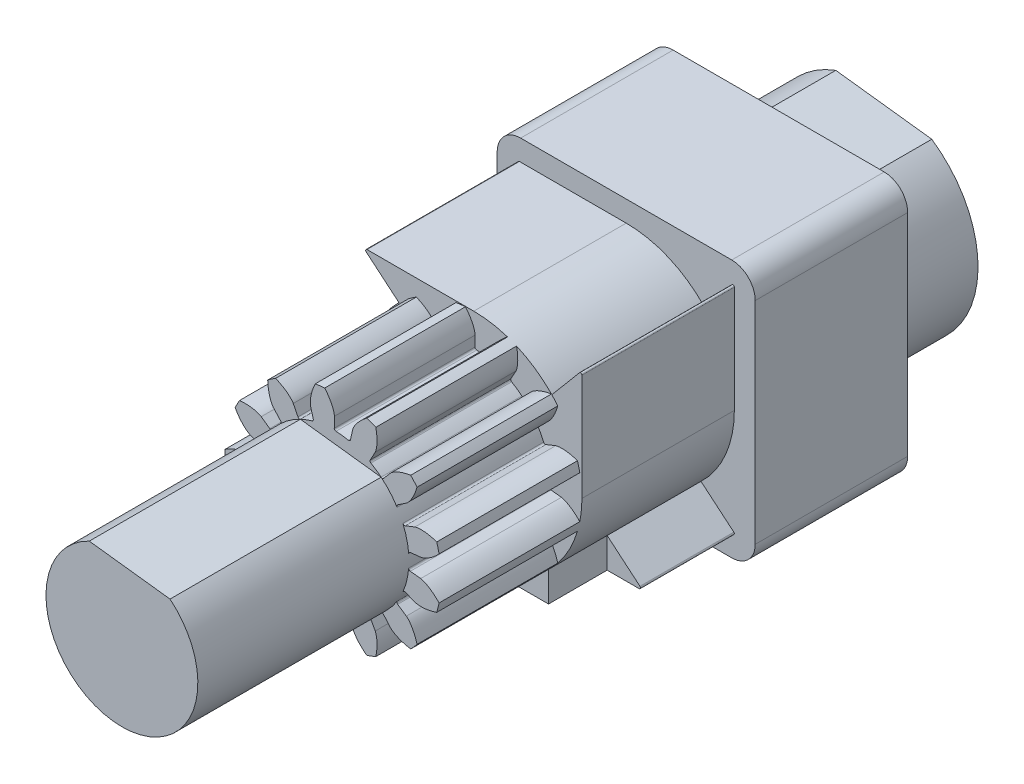
SolidWorks part; units mm, degrees
ref_plane "Front Plane" through (0, 0, 0) normal (0, 0, 1) x (1, 0, 0)
ref_plane "Top Plane" through (0, 0, 0) normal (0, 1, 0) x (1, 0, 0)
ref_plane "Right Plane" through (0, 0, 0) normal (1, 0, 0) x (0, 0, -1)
sketch "D" plane through (0, 0, 0) normal (0, 0, 1) x (1, 0, 0)
  line L0 (0, 0) -> (16, 0) construction
  circle A0 centre (0, 0) radius 4 construction
  dimension "D2" = 16
sketch "De, Di, Db" plane through (0, 0, 0) normal (0, 0, 1) x (1, 0, 0)
  circle A0 centre (0, 0) radius 3.7588 construction
  circle A1 centre (0, 0) radius 4.61 construction
  circle A2 centre (0, 0) radius 3.2375 construction
  point P7 (0, 0)
  dimension "D1" = 7.5175
  dimension "D2" = 9.22
  dimension "D3" = 6.475
sketch "Sketch4" plane through (0, 0, 0) normal (0, 0, 1) x (1, 0, 0)
  circle A0 centre (0, 0) radius 4.61 construction
  circle A1 centre (0, 0) radius 4.61
extrude "Addendum Extruded" add sketch "Sketch4" along normal mid plane 6
sketch "Tooth Profile Curve" plane through (0, 0, 0) normal (0, 0, 1) x (1, 0, 0)
  line L0 (0, 0) -> (4.61, 0) construction
  line L1 (0, 0) -> (3.7381, 0.3937) construction
  line L2 (0, 0) -> (3.9713, 0.4779) construction
  line L3 (3.7381, 0.3937) -> (3.2197, 0.3391)
  line L4 (3.2375, 0) -> (4.61, 0)
  circle A0 centre (0, 0) radius 3.7588 construction
  circle A1 centre (0, 0) radius 4.61 construction
  circle A2 centre (0, 0) radius 3.2375 construction
  circle A3 centre (0, 0) radius 4 construction
  arc A4 (3.2197, 0.3391) -> (3.2375, 0) centre (0, 0) cw
  arc A5 (4.61, 0) -> (4.5206, 0.9037) centre (0, 0) ccw
  spline S0 degree 4 poles (3.7381, 0.3937) (3.7409, 0.3941) (3.7486, 0.3952) (3.763, 0.3981) (3.7864, 0.4038) (3.8294, 0.4166) (3.8801, 0.4354) (3.9361, 0.4599) (3.995, 0.4897) (4.0445, 0.5171) (4.093, 0.5463) (4.1404, 0.5771) (4.1969, 0.6162) (4.2631, 0.6658) (4.3382, 0.7275) (4.4204, 0.8017) (4.501, 0.8819) (4.5775, 0.9643) (4.6515, 1.0515) (4.7207, 1.1386) (4.7888, 1.2329) (4.8499, 1.3219) (4.9141, 1.4255) (4.9647, 1.5102) (5.0267, 1.626) (5.062, 1.6955) (5.1015, 1.7782) (5.1182, 1.8155) (5.1285, 1.8385) knots 0 0 0 0 0 0.005377 0.015084 0.028532 0.04661 0.092111 0.119476 0.146842 0.174209 0.201575 0.228941 0.256307 0.307035 0.361767 0.4165 0.471232 0.525964 0.580697 0.635429 0.690161 0.744894 0.799626 0.854358 0.909091 0.954545 1 1 1 1 1 construction
  spline S1 degree 4 poles (3.7381, 0.3937) (3.7409, 0.3941) (3.7486, 0.3952) (3.763, 0.3981) (3.7864, 0.4038) (3.8294, 0.4166) (3.8801, 0.4354) (3.9361, 0.4599) (3.995, 0.4897) (4.0445, 0.5171) (4.093, 0.5463) (4.1404, 0.5771) (4.1969, 0.6162) (4.2631, 0.6658) (4.3382, 0.7275) (4.4204, 0.8017) (4.501, 0.8819) (4.5775, 0.9643) (4.6515, 1.0515) (4.7207, 1.1386) (4.7888, 1.2329) (4.8499, 1.3219) (4.9141, 1.4255) (4.9647, 1.5102) (5.0133, 1.6009) (5.0364, 1.6455) (5.048, 1.6684) knots 0 0 0 0 0 0.005377 0.015084 0.028532 0.04661 0.092111 0.119476 0.146842 0.174209 0.201575 0.228941 0.256307 0.307035 0.361767 0.4165 0.471232 0.525964 0.580697 0.635429 0.690161 0.744894 0.799626 0.854358 0.909091 0.909091 0.909091 0.909091 0.909091
  dimension "D1" = 6.863
  dimension "D2" = 0.85
  dimension "D3" = 6.013
extrude "1/2 Tooth Cut" cut sketch "Tooth Profile Curve" against normal mid plane 6 contours S1 L3 L4 region at (4.031, 0.2836, 0)
ref_plane "Plane of Mirroring" through (0, 0, 0) normal (0, 1, 0) x (1, 0, 0)
mirror "Mirror Tooth Cut" about plane through (0, 0, 0) normal (0, 1, 0) of "1/2 Tooth Cut"
fillet "Roots Fillet" radius 0.0762 2 edges at (3.2197, -0.3391, 0) (3.2197, 0.3391, 0)
pattern_circular "Circular Pattern of Teeth" count 13 over 360 about axis through (0, 0, -3) along (0, 0, 1) of "Mirror Tooth Cut", "1/2 Tooth Cut", "Roots Fillet" reverse direction yes
sketch "Sketch5" plane through (0, 0, 0) normal (0, 0, 1) x (1, 0, 0)
  line L0 (1, 4) -> (-1, 4) construction
  line L1 (-1, 5) -> (1, 5)
  line L2 (-1, 5) -> (-1, 3.873)
  line L5 (1, 4) -> (1, 5)
  line L6 (1, 4) -> (1, 3.873)
  arc A0 (-1, 3.873) -> (1, 3.873) centre (0, 0) ccw
  circle A1 centre (0, 0) radius 4 construction
  point P9 (0, 5)
  dimension "D1" = 8
  dimension "D2" = 1
  dimension "D3" = 2
sketch "Sketch6" [suppressed] plane through (0, 0, 0) normal (0, 0, 1) x (1, 0, 0)
  line L6 (41.8591, 5.9947) -> (34.5048, 4.9415) construction
  line L7 (37.3883, 19.7543) -> (30.8195, 16.2837) construction
  line L8 (41.8591, 5.9947) -> (34.5048, 4.9415)
  line L9 (37.3883, 19.7543) -> (30.8195, 16.2837)
  arc A14 (52.1159, 14.1398) -> (50.4738, 19.1936) centre (0, 0) ccw construction
  arc A20 (34.5048, 4.9415) -> (33.5461, 3.7044) centre (34.6643, 3.8278) ccw construction
  arc A29 (29.3167, 16.721) -> (30.8195, 16.2837) centre (30.294, 17.2784) ccw construction
  circle A30 centre (0, 0) radius 33.75 construction
  arc A31 (52.1159, 14.1398) -> (50.4738, 19.1936) centre (0, 0) ccw
  arc A32 (34.5048, 4.9415) -> (33.5461, 3.7044) centre (34.6643, 3.8278) ccw
  arc A33 (29.3167, 16.721) -> (30.8195, 16.2837) centre (30.294, 17.2784) ccw
  arc A34 (29.3167, 16.721) -> (33.5461, 3.7044) centre (0, 0) ccw
  spline S2 degree 4 poles (965.1968, -1751.9554) (49.5722, -17.509) (34.0199, 17.1415) (35.6787, 19.1473) (37.9033, 19.963) (38.3849, 20.1134) (39.1305, 20.2925) (39.9677, 20.4275) (40.8649, 20.5145) (41.6597, 20.5534) (42.2962, 20.5635) (43.0686, 20.5519) (43.9989, 20.5031) (45.0849, 20.3985) (46.322, 20.2188) (47.5725, 19.978) (64.8653, 15.8708) (78.7396, -0.7897) (70.5074, -3.2513) (1756.2094, -1025.0114) knots -0.360808 -0.360808 -0.360808 -0.360808 -0.360808 0.005377 0.015084 0.028532 0.04661 0.092111 0.146842 0.174209 0.201575 0.228941 0.256307 0.307035 0.361767 0.4165 0.471232 0.525964 3.418372 3.418372 3.418372 3.418372 3.418372 only from (37.3883, 19.7543) to (50.4738, 19.1936) construction
  spline S3 degree 4 poles (-248.913, 1984.6901) (29.8132, 43.3029) (37.5982, 6.1286) (40.1192, 5.4809) (42.3983, 6.1286) (42.8764, 6.29) (43.5848, 6.5834) (44.3415, 6.9662) (45.1185, 7.4233) (45.7844, 7.859) (46.3053, 8.2249) (46.9233, 8.6882) (47.6473, 9.2745) (48.4644, 9.9975) (49.3596, 10.87) (50.2297, 11.7999) (61.8058, 25.2872) (63.2375, 46.9208) (55.1306, 44.0736) (818.3166, 1861.5256) knots -0.360808 -0.360808 -0.360808 -0.360808 -0.360808 0.005377 0.015084 0.028532 0.04661 0.092111 0.146842 0.174209 0.201575 0.228941 0.256307 0.307035 0.361767 0.4165 0.471232 0.525964 3.418372 3.418372 3.418372 3.418372 3.418372 only from (41.8591, 5.9947) to (52.1159, 14.1398) construction
  spline S4 degree 4 poles (37.3883, 19.7543) (37.4162, 19.7684) (37.4955, 19.8059) (37.6488, 19.8697) (37.9033, 19.963) (38.3849, 20.1134) (39.1305, 20.2925) (39.9677, 20.4275) (40.8649, 20.5145) (41.6597, 20.5534) (42.2962, 20.5635) (43.0686, 20.5519) (43.9989, 20.5031) (45.0849, 20.3985) (46.322, 20.2188) (47.5725, 19.978) (48.7682, 19.694) (49.6459, 19.4492) (50.2125, 19.2764) (50.4738, 19.1936) knots 0 0 0 0 0 0.005377 0.015084 0.028532 0.04661 0.092111 0.146842 0.174209 0.201575 0.228941 0.256307 0.307035 0.361767 0.4165 0.471232 0.525964 0.573123 0.573123 0.573123 0.573123 0.573123
  spline S5 degree 4 poles (41.8591, 5.9947) (41.8899, 5.9998) (41.9761, 6.016) (42.1376, 6.0545) (42.3983, 6.1286) (42.8764, 6.29) (43.5848, 6.5834) (44.3415, 6.9662) (45.1185, 7.4233) (45.7844, 7.859) (46.3053, 8.2249) (46.9233, 8.6882) (47.6473, 9.2745) (48.4644, 9.9975) (49.3596, 10.87) (50.2297, 11.7999) (51.0302, 12.7325) (51.5963, 13.4464) (51.9531, 13.9192) (52.1159, 14.1398) knots 0 0 0 0 0 0.005377 0.015084 0.028532 0.04661 0.092111 0.146842 0.174209 0.201575 0.228941 0.256307 0.307035 0.361767 0.4165 0.471232 0.525964 0.573123 0.573123 0.573123 0.573123 0.573123
extrude "Teeth Removing" [suppressed] cut sketch "Sketch6" against normal through all both flip side to cut
sketch "Sketch7" [suppressed] plane through (0, 0, 0) normal (0, 0, 1) x (1, 0, 0)
  line L0 (-3, 10) -> (3, 10)
  line L1 (3, 10) -> (3, 7.4162)
  line L2 (-3, 10) -> (-3, 7.4162)
  arc A0 (-3, 7.4162) -> (3, 7.4162) centre (0, 0) ccw
  point P1 (0, 10)
  dimension "D1" = 8
  dimension "D2" = 10
  dimension "D3" = 6
extrude "Cut-Extrude1" [suppressed] cut sketch "Sketch7" against normal through all both and the other way through all
sketch "Sketch8" [suppressed] plane through (0, 0, 0) normal (0, 0, 1) x (1, 0, 0)
  line L0 (-4.8226, 27.7752) -> (-3.9753, 22.8953) construction
  line L1 (4.8226, 27.7752) -> (3.9753, 22.8953) construction
  line L2 (-4.8226, 27.7752) -> (-3.9753, 22.8953)
  line L3 (4.8226, 27.7752) -> (3.9753, 22.8953)
  arc A0 (-4.5622, 22.0326) -> (4.5622, 22.0326) centre (0, 0) ccw
  arc A1 (-4.5622, 22.0326) -> (-3.9753, 22.8953) centre (-4.7142, 22.767) ccw construction
  arc A2 (3.9753, 22.8953) -> (4.5622, 22.0326) centre (4.7142, 22.767) ccw construction
  arc A3 (-4.5622, 22.0326) -> (-3.9753, 22.8953) centre (-4.7142, 22.767) ccw
  arc A4 (3.9753, 22.8953) -> (4.5622, 22.0326) centre (4.7142, 22.767) ccw
  arc A5 (-1.7713, 35.9564) -> (1.7713, 35.9564) centre (0, 0) cw
  spline S0 degree 4 poles (-2951.1447, 536.0596) (-42.0553, 30.3098) (3.4186, 24.472) (4.7778, 26.2412) (4.8488, 28.1447) (4.8449, 28.481) (4.8049, 28.9907) (4.718, 29.5493) (4.5883, 30.1361) (4.4492, 30.6481) (4.3245, 31.0537) (4.1581, 31.541) (3.9355, 32.1209) (3.6454, 32.7879) (3.2766, 33.5352) (2.8663, 34.2784) (-4.9345, 47.0779) (-24.4948, 52.3174) (-14.1166, 37.6796) (-2283.6828, 1979.2083) knots -0.444693 -0.444693 -0.444693 -0.444693 -0.444693 0.005377 0.015084 0.028532 0.04661 0.092111 0.146842 0.174209 0.201575 0.228941 0.256307 0.307035 0.361767 0.4165 0.471232 0.525964 4.228351 4.228351 4.228351 4.228351 4.228351 only from (4.8226, 27.7752) to (1.7713, 35.9564) construction
  spline S1 degree 4 poles (2951.1447, 536.0596) (42.0553, 30.3098) (-3.4186, 24.472) (-4.7778, 26.2412) (-4.8488, 28.1447) (-4.8449, 28.481) (-4.8049, 28.9907) (-4.718, 29.5493) (-4.5883, 30.1361) (-4.4492, 30.6481) (-4.3245, 31.0537) (-4.1581, 31.541) (-3.9355, 32.1209) (-3.6454, 32.7879) (-3.2766, 33.5352) (-2.8663, 34.2784) (4.9345, 47.0779) (24.4948, 52.3174) (14.1166, 37.6796) (2283.6828, 1979.2083) knots -0.444693 -0.444693 -0.444693 -0.444693 -0.444693 0.005377 0.015084 0.028532 0.04661 0.092111 0.146842 0.174209 0.201575 0.228941 0.256307 0.307035 0.361767 0.4165 0.471232 0.525964 4.228351 4.228351 4.228351 4.228351 4.228351 only from (-4.8226, 27.7752) to (-1.7713, 35.9564) construction
  spline S2 degree 4 poles (4.8226, 27.7752) (4.8257, 27.7958) (4.8332, 27.8538) (4.842, 27.9641) (4.8488, 28.1447) (4.8449, 28.481) (4.8049, 28.9907) (4.718, 29.5493) (4.5883, 30.1361) (4.4492, 30.6481) (4.3245, 31.0537) (4.1581, 31.541) (3.9355, 32.1209) (3.6454, 32.7879) (3.2766, 33.5352) (2.8663, 34.2784) (2.4399, 34.9781) (2.1039, 35.4841) (1.8776, 35.8078) (1.7713, 35.9564) knots 0 0 0 0 0 0.005377 0.015084 0.028532 0.04661 0.092111 0.146842 0.174209 0.201575 0.228941 0.256307 0.307035 0.361767 0.4165 0.471232 0.525964 0.573122 0.573122 0.573122 0.573122 0.573122
  spline S3 degree 4 poles (-4.8226, 27.7752) (-4.8257, 27.7958) (-4.8332, 27.8538) (-4.842, 27.9641) (-4.8488, 28.1447) (-4.8449, 28.481) (-4.8049, 28.9907) (-4.718, 29.5493) (-4.5883, 30.1361) (-4.4492, 30.6481) (-4.3245, 31.0537) (-4.1581, 31.541) (-3.9355, 32.1209) (-3.6454, 32.7879) (-3.2766, 33.5352) (-2.8663, 34.2784) (-2.4399, 34.9781) (-2.1039, 35.4841) (-1.8776, 35.8078) (-1.7713, 35.9564) knots 0 0 0 0 0 0.005377 0.015084 0.028532 0.04661 0.092111 0.146842 0.174209 0.201575 0.228941 0.256307 0.307035 0.361767 0.4165 0.471232 0.525964 0.573122 0.573122 0.573122 0.573122 0.573122
extrude "Cut-Extrude2" [suppressed] cut sketch "Sketch8" against normal through all both and the other way through all flip side to cut
sketch "Sketch9" [suppressed] plane through (0, 0, 0) normal (0, 0, 1) x (1, 0, 0)
  circle A0 centre (0, 0) radius 4
  dimension "D1" = 8
extrude "Cut-Extrude3" [suppressed] cut sketch "Sketch9" against normal through all both and the other way through all
sketch "Sketch10" [suppressed] plane through (0, 0, 0) normal (0, 0, 1) x (1, 0, 0)
  circle A0 centre (0, 0) radius 6
  dimension "D1" = 12
extrude "Cut-Extrude4" [suppressed] cut sketch "Sketch10" against normal through all both and the other way through all
sketch "Sketch11" [suppressed] plane through (0, 0, 0) normal (0, 0, 1) x (1, 0, 0)
  line L0 (27.9061, 3.9965) -> (23.0032, 3.2943) construction
  line L1 (24.9255, 13.1696) -> (20.5463, 10.8558) construction
  line L2 (-4.8226, 27.7752) -> (-3.9753, 22.8953) construction
  line L3 (4.8226, 27.7752) -> (3.9753, 22.8953) construction
  line L4 (27.9061, 3.9965) -> (23.0032, 3.2943)
  line L5 (24.9255, 13.1696) -> (20.5463, 10.8558)
  line L6 (-4.8226, 27.7752) -> (-3.9753, 22.8953)
  line L7 (4.8226, 27.7752) -> (3.9753, 22.8953)
  arc A0 (-4.5622, 22.0326) -> (22.3641, 2.4696) centre (0, 0) ccw
  arc A1 (19.5445, 11.1473) -> (20.5463, 10.8558) centre (20.196, 11.5189) ccw construction
  arc A2 (23.0032, 3.2943) -> (22.3641, 2.4696) centre (23.1095, 2.5519) ccw construction
  arc A4 (3.9753, 22.8953) -> (4.5622, 22.0326) centre (4.7142, 22.767) ccw construction
  arc A5 (19.5445, 11.1473) -> (20.5463, 10.8558) centre (20.196, 11.5189) ccw
  arc A6 (23.0032, 3.2943) -> (22.3641, 2.4696) centre (23.1095, 2.5519) ccw
  arc A7 (-4.5622, 22.0326) -> (-3.9753, 22.8953) centre (-4.7142, 22.767) ccw construction
  arc A8 (3.9753, 22.8953) -> (4.5622, 22.0326) centre (4.7142, 22.767) ccw
  arc A9 (19.5445, 11.1473) -> (4.5622, 22.0326) centre (0, 0) ccw
  arc A10 (-1.7713, 35.9564) -> (1.7713, 35.9564) centre (0, 0) cw
  arc A11 (33.6492, 12.7957) -> (34.7439, 9.4265) centre (0, 0) cw
  arc A12 (-4.5622, 22.0326) -> (-3.9753, 22.8953) centre (-4.7142, 22.767) ccw
  spline S0 degree 4 poles (-402.1308, 2972.3569) (15.8305, 49.3632) (24.3306, 4.311) (26.4333, 3.565) (28.2656, 4.0857) (28.5842, 4.1933) (29.0566, 4.3889) (29.561, 4.6441) (30.079, 4.9488) (30.5229, 5.2393) (30.8702, 5.4833) (31.2822, 5.7922) (31.7649, 6.183) (32.3096, 6.665) (32.9064, 7.2467) (33.4865, 7.8666) (43.2489, 19.2409) (42.1875, 39.4629) (31.4732, 25.0693) (1176.6422, 2783.5204) knots -0.444693 -0.444693 -0.444693 -0.444693 -0.444693 0.005377 0.015084 0.028532 0.04661 0.092111 0.146842 0.174209 0.201575 0.228941 0.256307 0.307035 0.361767 0.4165 0.471232 0.525964 4.228351 4.228351 4.228351 4.228351 4.228351 only from (27.9061, 3.9965) to (34.7439, 9.4265) construction
  spline S1 degree 4 poles (1421.7769, -2641.0538) (41.8221, -30.6307) (22.2178, 10.8135) (23.4804, 12.6529) (25.2689, 13.3086) (25.5899, 13.4089) (26.087, 13.5283) (26.6451, 13.6183) (27.2433, 13.6763) (27.7732, 13.7022) (28.1975, 13.709) (28.7124, 13.7013) (29.3326, 13.6688) (30.0566, 13.599) (30.8813, 13.4792) (31.715, 13.3187) (46.2986, 9.8549) (57.3261, -7.129) (40.1977, -1.782) (2588.0358, -1560.3024) knots -0.444693 -0.444693 -0.444693 -0.444693 -0.444693 0.005377 0.015084 0.028532 0.04661 0.092111 0.146842 0.174209 0.201575 0.228941 0.256307 0.307035 0.361767 0.4165 0.471232 0.525964 4.228351 4.228351 4.228351 4.228351 4.228351 only from (24.9255, 13.1696) to (33.6492, 12.7957) construction
  spline S2 degree 4 poles (2951.1447, 536.0596) (42.0553, 30.3098) (-3.4186, 24.472) (-4.7778, 26.2412) (-4.8488, 28.1447) (-4.8449, 28.481) (-4.8049, 28.9907) (-4.718, 29.5493) (-4.5883, 30.1361) (-4.4492, 30.6481) (-4.3245, 31.0537) (-4.1581, 31.541) (-3.9355, 32.1209) (-3.6454, 32.7879) (-3.2766, 33.5352) (-2.8663, 34.2784) (4.9345, 47.0779) (24.4948, 52.3174) (14.1166, 37.6796) (2283.6828, 1979.2083) knots -0.444693 -0.444693 -0.444693 -0.444693 -0.444693 0.005377 0.015084 0.028532 0.04661 0.092111 0.146842 0.174209 0.201575 0.228941 0.256307 0.307035 0.361767 0.4165 0.471232 0.525964 4.228351 4.228351 4.228351 4.228351 4.228351 only from (-4.8226, 27.7752) to (-1.7713, 35.9564) construction
  spline S3 degree 4 poles (-2951.1447, 536.0596) (-42.0553, 30.3098) (3.4186, 24.472) (4.7778, 26.2412) (4.8488, 28.1447) (4.8449, 28.481) (4.8049, 28.9907) (4.718, 29.5493) (4.5883, 30.1361) (4.4492, 30.6481) (4.3245, 31.0537) (4.1581, 31.541) (3.9355, 32.1209) (3.6454, 32.7879) (3.2766, 33.5352) (2.8663, 34.2784) (-4.9345, 47.0779) (-24.4948, 52.3174) (-14.1166, 37.6796) (-2283.6828, 1979.2083) knots -0.444693 -0.444693 -0.444693 -0.444693 -0.444693 0.005377 0.015084 0.028532 0.04661 0.092111 0.146842 0.174209 0.201575 0.228941 0.256307 0.307035 0.361767 0.4165 0.471232 0.525964 4.228351 4.228351 4.228351 4.228351 4.228351 only from (4.8226, 27.7752) to (1.7713, 35.9564) construction
  spline S4 degree 4 poles (27.9061, 3.9965) (27.9266, 3.9998) (27.9841, 4.0106) (28.0917, 4.0363) (28.2656, 4.0857) (28.5842, 4.1933) (29.0566, 4.3889) (29.561, 4.6441) (30.079, 4.9488) (30.5229, 5.2393) (30.8702, 5.4833) (31.2822, 5.7922) (31.7649, 6.183) (32.3096, 6.665) (32.9064, 7.2467) (33.4865, 7.8666) (34.0201, 8.4883) (34.3975, 8.9643) (34.6354, 9.2795) (34.7439, 9.4265) knots 0 0 0 0 0 0.005377 0.015084 0.028532 0.04661 0.092111 0.146842 0.174209 0.201575 0.228941 0.256307 0.307035 0.361767 0.4165 0.471232 0.525964 0.573122 0.573122 0.573122 0.573122 0.573122
  spline S5 degree 4 poles (24.9255, 13.1696) (24.9442, 13.1789) (24.997, 13.204) (25.0992, 13.2464) (25.2689, 13.3086) (25.5899, 13.4089) (26.087, 13.5283) (26.6451, 13.6183) (27.2433, 13.6763) (27.7732, 13.7022) (28.1975, 13.709) (28.7124, 13.7013) (29.3326, 13.6688) (30.0566, 13.599) (30.8813, 13.4792) (31.715, 13.3187) (32.5122, 13.1293) (33.0972, 12.9661) (33.475, 12.8509) (33.6492, 12.7957) knots 0 0 0 0 0 0.005377 0.015084 0.028532 0.04661 0.092111 0.146842 0.174209 0.201575 0.228941 0.256307 0.307035 0.361767 0.4165 0.471232 0.525964 0.573122 0.573122 0.573122 0.573122 0.573122
  spline S6 degree 4 poles (-4.8226, 27.7752) (-4.8257, 27.7958) (-4.8332, 27.8538) (-4.842, 27.9641) (-4.8488, 28.1447) (-4.8449, 28.481) (-4.8049, 28.9907) (-4.718, 29.5493) (-4.5883, 30.1361) (-4.4492, 30.6481) (-4.3245, 31.0537) (-4.1581, 31.541) (-3.9355, 32.1209) (-3.6454, 32.7879) (-3.2766, 33.5352) (-2.8663, 34.2784) (-2.4399, 34.9781) (-2.1039, 35.4841) (-1.8776, 35.8078) (-1.7713, 35.9564) knots 0 0 0 0 0 0.005377 0.015084 0.028532 0.04661 0.092111 0.146842 0.174209 0.201575 0.228941 0.256307 0.307035 0.361767 0.4165 0.471232 0.525964 0.573122 0.573122 0.573122 0.573122 0.573122
  spline S7 degree 4 poles (4.8226, 27.7752) (4.8257, 27.7958) (4.8332, 27.8538) (4.842, 27.9641) (4.8488, 28.1447) (4.8449, 28.481) (4.8049, 28.9907) (4.718, 29.5493) (4.5883, 30.1361) (4.4492, 30.6481) (4.3245, 31.0537) (4.1581, 31.541) (3.9355, 32.1209) (3.6454, 32.7879) (3.2766, 33.5352) (2.8663, 34.2784) (2.4399, 34.9781) (2.1039, 35.4841) (1.8776, 35.8078) (1.7713, 35.9564) knots 0 0 0 0 0 0.005377 0.015084 0.028532 0.04661 0.092111 0.146842 0.174209 0.201575 0.228941 0.256307 0.307035 0.361767 0.4165 0.471232 0.525964 0.573122 0.573122 0.573122 0.573122 0.573122
extrude "Cut-Extrude6" [suppressed] cut sketch "Sketch11" against normal through all both and the other way through all flip side to cut
sketch "Sketch12" [suppressed] plane through (0, 0, 0) normal (0, 0, 1) x (1, 0, 0)
  line L0 (-20.2274, -19.636) -> (-16.6736, -16.1861) construction
  line L1 (-12.4243, -25.3053) -> (-10.2415, -20.8593) construction
  line L2 (4.8226, 27.7752) -> (3.9753, 22.8953) construction
  line L3 (-4.8226, 27.7752) -> (-3.9753, 22.8953) construction
  line L4 (-20.2274, -19.636) -> (-16.6736, -16.1861)
  line L5 (-12.4243, -25.3053) -> (-10.2415, -20.8593)
  line L6 (4.8226, 27.7752) -> (3.9753, 22.8953)
  line L7 (-4.8226, 27.7752) -> (-3.9753, 22.8953)
  arc A0 (-9.2596, -20.5063) -> (4.5622, 22.0326) centre (0, 0) ccw
  arc A1 (-9.2596, -20.5063) -> (-10.2415, -20.8593) centre (-9.5682, -21.1899) ccw construction
  arc A2 (-16.6736, -16.1861) -> (-16.6413, -15.1432) centre (-17.196, -15.648) ccw construction
  arc A3 (-4.5622, 22.0326) -> (-3.9753, 22.8953) centre (-4.7142, 22.767) ccw construction
  arc A4 (3.9753, 22.8953) -> (4.5622, 22.0326) centre (4.7142, 22.767) ccw construction
  arc A5 (-9.2596, -20.5063) -> (-10.2415, -20.8593) centre (-9.5682, -21.1899) ccw
  arc A6 (-16.6736, -16.1861) -> (-16.6413, -15.1432) centre (-17.196, -15.648) ccw
  arc A7 (-4.5622, 22.0326) -> (-3.9753, 22.8953) centre (-4.7142, 22.767) ccw
  arc A8 (3.9753, 22.8953) -> (4.5622, 22.0326) centre (4.7142, 22.767) ccw
  arc A9 (-4.5622, 22.0326) -> (-16.6413, -15.1432) centre (0, 0) ccw
  arc A10 (1.7713, 35.9564) -> (-1.7713, 35.9564) centre (0, 0) ccw
  arc A11 (-19.7016, -30.1305) -> (-22.5676, -28.0482) centre (0, 0) cw
  spline S0 degree 4 poles (2072.4383, -2168.3207) (16.2078, -49.2406) (-17.15, -17.7889) (-19.2895, -18.4213) (-20.4658, -19.9195) (-20.6604, -20.1939) (-20.9275, -20.6297) (-21.1856, -21.1327) (-21.4256, -21.6837) (-21.614, -22.1796) (-21.7515, -22.5811) (-21.9033, -23.0732) (-22.064, -23.6731) (-22.2214, -24.3832) (-22.3623, -25.2046) (-22.4673, -26.0471) (-23.6796, -40.9873) (-10.9347, -56.7234) (-10.727, -38.7809) (684.1887, -2943.5283) knots -0.444693 -0.444693 -0.444693 -0.444693 -0.444693 0.005377 0.015084 0.028532 0.04661 0.092111 0.146842 0.174209 0.201575 0.228941 0.256307 0.307035 0.361767 0.4165 0.471232 0.525964 4.228351 4.228351 4.228351 4.228351 4.228351 only from (-20.2274, -19.636) to (-22.5676, -28.0482) construction
  spline S1 degree 4 poles (-2702.6142, 1300.958) (-51.8391, 0.1983) (-11.6186, -21.8076) (-11.5589, -24.0379) (-12.6203, -25.6196) (-12.8211, -25.8894) (-13.1531, -26.2782) (-13.5517, -26.6791) (-14.0016, -27.0776) (-14.415, -27.41) (-14.7543, -27.6649) (-15.1754, -27.9613) (-15.6963, -28.2995) (-16.323, -28.6687) (-17.0606, -29.0565) (-17.8295, -29.4166) (-31.6638, -35.1864) (-50.5681, -27.928) (-33.5681, -22.1859) (-3010.8877, -258.8981) knots -0.444693 -0.444693 -0.444693 -0.444693 -0.444693 0.005377 0.015084 0.028532 0.04661 0.092111 0.146842 0.174209 0.201575 0.228941 0.256307 0.307035 0.361767 0.4165 0.471232 0.525964 4.228351 4.228351 4.228351 4.228351 4.228351 only from (-12.4243, -25.3053) to (-19.7016, -30.1305) construction
  spline S2 degree 4 poles (2951.1447, 536.0596) (42.0553, 30.3098) (-3.4186, 24.472) (-4.7778, 26.2412) (-4.8488, 28.1447) (-4.8449, 28.481) (-4.8049, 28.9907) (-4.718, 29.5493) (-4.5883, 30.1361) (-4.4492, 30.6481) (-4.3245, 31.0537) (-4.1581, 31.541) (-3.9355, 32.1209) (-3.6454, 32.7879) (-3.2766, 33.5352) (-2.8663, 34.2784) (4.9345, 47.0779) (24.4948, 52.3174) (14.1166, 37.6796) (2283.6828, 1979.2083) knots -0.444693 -0.444693 -0.444693 -0.444693 -0.444693 0.005377 0.015084 0.028532 0.04661 0.092111 0.146842 0.174209 0.201575 0.228941 0.256307 0.307035 0.361767 0.4165 0.471232 0.525964 4.228351 4.228351 4.228351 4.228351 4.228351 only from (-4.8226, 27.7752) to (-1.7713, 35.9564) construction
  spline S3 degree 4 poles (-2951.1447, 536.0596) (-42.0553, 30.3098) (3.4186, 24.472) (4.7778, 26.2412) (4.8488, 28.1447) (4.8449, 28.481) (4.8049, 28.9907) (4.718, 29.5493) (4.5883, 30.1361) (4.4492, 30.6481) (4.3245, 31.0537) (4.1581, 31.541) (3.9355, 32.1209) (3.6454, 32.7879) (3.2766, 33.5352) (2.8663, 34.2784) (-4.9345, 47.0779) (-24.4948, 52.3174) (-14.1166, 37.6796) (-2283.6828, 1979.2083) knots -0.444693 -0.444693 -0.444693 -0.444693 -0.444693 0.005377 0.015084 0.028532 0.04661 0.092111 0.146842 0.174209 0.201575 0.228941 0.256307 0.307035 0.361767 0.4165 0.471232 0.525964 4.228351 4.228351 4.228351 4.228351 4.228351 only from (4.8226, 27.7752) to (1.7713, 35.9564) construction
  spline S4 degree 4 poles (-20.2274, -19.636) (-20.2421, -19.6508) (-20.2822, -19.6933) (-20.3542, -19.7774) (-20.4658, -19.9195) (-20.6604, -20.1939) (-20.9275, -20.6297) (-21.1856, -21.1327) (-21.4256, -21.6837) (-21.614, -22.1796) (-21.7515, -22.5811) (-21.9033, -23.0732) (-22.064, -23.6731) (-22.2214, -24.3832) (-22.3623, -25.2046) (-22.4673, -26.0471) (-22.5335, -26.8637) (-22.5591, -27.4706) (-22.5663, -27.8654) (-22.5676, -28.0482) knots 0 0 0 0 0 0.005377 0.015084 0.028532 0.04661 0.092111 0.146842 0.174209 0.201575 0.228941 0.256307 0.307035 0.361767 0.4165 0.471232 0.525964 0.573122 0.573122 0.573122 0.573122 0.573122
  spline S5 degree 4 poles (-12.4243, -25.3053) (-12.4339, -25.3238) (-12.4619, -25.3751) (-12.5196, -25.4695) (-12.6203, -25.6196) (-12.8211, -25.8894) (-13.1531, -26.2782) (-13.5517, -26.6791) (-14.0016, -27.0776) (-14.415, -27.41) (-14.7543, -27.6649) (-15.1754, -27.9613) (-15.6963, -28.2995) (-16.323, -28.6687) (-17.0606, -29.0565) (-17.8295, -29.4166) (-18.5857, -29.732) (-19.1549, -29.9439) (-19.5282, -30.0727) (-19.7016, -30.1305) knots 0 0 0 0 0 0.005377 0.015084 0.028532 0.04661 0.092111 0.146842 0.174209 0.201575 0.228941 0.256307 0.307035 0.361767 0.4165 0.471232 0.525964 0.573122 0.573122 0.573122 0.573122 0.573122
  spline S6 degree 4 poles (-4.8226, 27.7752) (-4.8257, 27.7958) (-4.8332, 27.8538) (-4.842, 27.9641) (-4.8488, 28.1447) (-4.8449, 28.481) (-4.8049, 28.9907) (-4.718, 29.5493) (-4.5883, 30.1361) (-4.4492, 30.6481) (-4.3245, 31.0537) (-4.1581, 31.541) (-3.9355, 32.1209) (-3.6454, 32.7879) (-3.2766, 33.5352) (-2.8663, 34.2784) (-2.4399, 34.9781) (-2.1039, 35.4841) (-1.8776, 35.8078) (-1.7713, 35.9564) knots 0 0 0 0 0 0.005377 0.015084 0.028532 0.04661 0.092111 0.146842 0.174209 0.201575 0.228941 0.256307 0.307035 0.361767 0.4165 0.471232 0.525964 0.573122 0.573122 0.573122 0.573122 0.573122
  spline S7 degree 4 poles (4.8226, 27.7752) (4.8257, 27.7958) (4.8332, 27.8538) (4.842, 27.9641) (4.8488, 28.1447) (4.8449, 28.481) (4.8049, 28.9907) (4.718, 29.5493) (4.5883, 30.1361) (4.4492, 30.6481) (4.3245, 31.0537) (4.1581, 31.541) (3.9355, 32.1209) (3.6454, 32.7879) (3.2766, 33.5352) (2.8663, 34.2784) (2.4399, 34.9781) (2.1039, 35.4841) (1.8776, 35.8078) (1.7713, 35.9564) knots 0 0 0 0 0 0.005377 0.015084 0.028532 0.04661 0.092111 0.146842 0.174209 0.201575 0.228941 0.256307 0.307035 0.361767 0.4165 0.471232 0.525964 0.573122 0.573122 0.573122 0.573122 0.573122
extrude "Cut-Extrude7" [suppressed] cut sketch "Sketch12" against normal through all both and the other way through all flip side to cut
sketch "Sketch14" plane through (0, 0, 3) normal (0, 0, 1) x (1, 0, 0)
  line L0 (-1.3919, 2.923) -> (2.051, 2.505)
  arc A0 (-1.3919, 2.923) -> (2.051, 2.505) centre (0, 0) ccw
  arc A1 (-0.8965, 3.1109) -> (-1.3919, 2.923) centre (0, 0) ccw construction
extrude "Boss-Extrude2" add sketch "Sketch14" along normal blind 9
sketch "Sketch15" plane through (0, 0, -3) normal (0, 0, -1) x (-1, 0, 0)
  circle A0 centre (0, 0) radius 4.61
  dimension "D1" = 9.22
extrude "Boss-Extrude3" add sketch "Sketch15" along normal blind 6.5
sketch "Sketch16" plane through (0, 0, -9.5) normal (0, 0, -1) x (-1, 0, 0)
  line L0 (-5.5, 4.5) -> (-5.5, -4.5)
  line L1 (-4.5, -5.5) -> (4.5, -5.5)
  line L2 (5.5, -4.5) -> (5.5, 4.5)
  line L3 (4.5, 5.5) -> (-4.5, 5.5)
  line L4 (0, 5.5) -> (0, 0) construction
  line L5 (0, 0) -> (-5.5, 0) construction
  line L6 (0, 0) -> (0, -5.5) construction
  arc A0 (-4.5, -5.5) -> (-5.5, -4.5) centre (-4.5, -4.5) cw
  arc A1 (4.5, -5.5) -> (5.5, -4.5) centre (4.5, -4.5) ccw
  arc A2 (5.5, 4.5) -> (4.5, 5.5) centre (4.5, 4.5) ccw
  arc A3 (-4.5, 5.5) -> (-5.5, 4.5) centre (-4.5, 4.5) ccw
  point P10 (-5.5, -5.5)
  point P18 (-5.5, 5.5)
  dimension "D2" = 1
  dimension "D1" = 11
extrude "Boss-Extrude4" add sketch "Sketch16" along normal blind 6.5
sketch "Sketch17" plane through (0, 0, -16) normal (0, 0, -1) x (-1, 0, 0)
  line L0 (-2.5287, 3.7223) -> (1.5644, 4.2193)
  line L1 (-2.051, 2.505) -> (1.3919, 2.923) construction
  line L2 (0, 0) -> (-0.4821, 3.9708) construction
  line L3 (-1.9476, 2.2819) -> (1.3449, 2.6817)
  arc A0 (-2.5287, 3.7223) -> (1.5644, 4.2193) centre (0, 0) ccw
  arc A1 (-1.9476, 2.2819) -> (1.3449, 2.6817) centre (0, 0) ccw
  dimension "D1" = 9
  dimension "D2" = 4
  dimension "D3" = 1.5
extrude "Boss-Extrude5" add sketch "Sketch17" along normal blind 4
sketch "Sketch18" plane through (0, 0, -9.5) normal (0, 0, 1) x (1, 0, 0)
  line L0 (0, 0) -> (0, 4.61) construction
  line L1 (0, 0) -> (4.61, 0) construction
  line L2 (0, 0) -> (-4.61, 0) construction
  line L3 (-4.61, -4.5487) -> (-4.61, 0)
  line L4 (-4.5487, 4.61) -> (0, 4.61)
  line L7 (-4.5873, 4.504) -> (-3.1881, 3.3299)
  line L11 (-4.5487, 4.55) -> (-4.5487, 5.5) construction
  line L12 (4.504, 4.5873) -> (3.3299, 3.1881)
  line L13 (-4.5487, 4.55) -> (-5.4987, 4.55) construction
  line L14 (-4.5, 5.5) -> (4.5, 5.5) construction
  line L17 (4.61, 4.5487) -> (4.61, 0)
  line L18 (4.5873, -4.504) -> (3.1881, -3.3299)
  line L19 (4.5487, -4.61) -> (0, -4.61)
  line L20 (-4.504, -4.5873) -> (-3.3299, -3.1881)
  line L21 (-4.61, -4.5487) -> (-4.61, 0)
  circle A0 centre (0, 0) radius 4.61 construction
  arc A3 (0, 4.61) -> (-3.1881, 3.3299) centre (0, 0) ccw
  arc A5 (-4.5873, 4.504) -> (-4.5487, 4.61) centre (-4.5487, 4.55) cw
  arc A6 (-2.7844, 3.6741) -> (-3.9829, 2.3213) centre (0, 0) ccw construction
  arc A7 (4.504, 4.5873) -> (4.61, 4.5487) centre (4.55, 4.5487) cw
  arc A8 (-4.5, 5.5) -> (-5.5, 4.5) centre (-4.5, 4.5) ccw construction
  arc A9 (4.61, 0) -> (3.3299, 3.1881) centre (0, 0) ccw
  arc A10 (4.5873, -4.504) -> (4.5487, -4.61) centre (4.5487, -4.55) cw
  arc A11 (0, -4.61) -> (3.1881, -3.3299) centre (0, 0) ccw
  arc A12 (-4.504, -4.5873) -> (-4.61, -4.5487) centre (-4.55, -4.5487) cw
  arc A13 (-4.61, 0) -> (-3.3299, -3.1881) centre (0, 0) ccw
  point P15 (-4.7136, 4.61)
  point P45 (0, 0)
  circle M29 centre (0, 0) radius 4.61
  dimension "D4" = 0.06
  dimension "D1" = 40
  dimension "D5" = 4
extrude "Boss-Extrude6" add sketch "Sketch18" along normal blind 4 contours A12 L20 L3 M29 | A10 L18 L19 M29 | A7 L12 L17 M29 | A5 L7 L4 M29 region at (-4.2129, -2.9668, -9.5) region at (-2.9668, 4.2129, -9.5) region at (2.9668, -4.2129, -9.5) region at (4.2129, 2.9668, -9.5)
sketch "Sketch19" plane through (0, 0, -5.5) normal (0, 0, 1) x (1, 0, 0)
  line L0 (3.1881, -3.3299) -> (3.1881, -4.61)
  line L2 (4.5873, -4.504) -> (3.1881, -3.3299)
  line L3 (0, -4.61) -> (4.5487, -4.61)
  line L4 (4.5873, -4.504) -> (3.1881, -3.3299)
  line L5 (3.1881, -4.61) -> (4.5487, -4.61)
  arc A2 (4.5487, -4.61) -> (4.5873, -4.504) centre (4.5487, -4.55) ccw
  arc A3 (0, -4.61) -> (3.1881, -3.3299) centre (0, 0) ccw
  arc A4 (4.5487, -4.61) -> (4.5873, -4.504) centre (4.5487, -4.55) ccw
  dimension "D1" = 0
extrude "Cut-Extrude8" cut sketch "Sketch19" against normal blind 3
sketch "Sketch20" plane through (0, 0, -16) normal (0, 0, -1) x (-1, 0, 0)
  line L1 (1.3449, 2.6817) -> (-1.9476, 2.2819)
  line L2 (1.3449, 2.6817) -> (-1.9476, 2.2819)
  arc A1 (-1.9476, 2.2819) -> (1.3449, 2.6817) centre (0, 0) ccw
  arc A2 (-1.9476, 2.2819) -> (1.3449, 2.6817) centre (0, 0) ccw
  dimension "D1" = 0
extrude "Cut-Extrude9" cut sketch "Sketch20" against normal blind 12
sketch "Sketch21" plane through (0, 0, -5.5) normal (0, 0, 1) x (1, 0, 0)
  line L0 (-4.5487, 4.61) -> (0, 4.61) construction
  line L1 (-4.5487, 4.61) -> (0, 4.61)
  line L2 (-4.61, -4.5487) -> (-4.61, 0) construction
  line L3 (-4.504, -4.5873) -> (-3.3299, -3.1881) construction
  line L4 (4.5487, -4.61) -> (0, -4.61) construction
  line L5 (3.1881, -4.61) -> (4.5487, -4.61) construction
  line L6 (4.5873, -4.504) -> (3.1881, -3.3299) construction
  line L7 (4.61, 4.5487) -> (4.61, 0) construction
  line L8 (4.504, 4.5873) -> (3.3299, 3.1881) construction
  line L9 (-4.5873, 4.504) -> (-3.1881, 3.3299) construction
  line L10 (-4.61, -4.5487) -> (-4.61, 0)
  line L11 (-4.504, -4.5873) -> (-3.3299, -3.1881)
  line L12 (4.5487, -4.61) -> (0, -4.61)
  line L13 (3.1881, -4.61) -> (4.5487, -4.61)
  line L14 (4.5873, -4.504) -> (3.1881, -3.3299)
  line L15 (4.61, 4.5487) -> (4.61, 0)
  line L16 (4.504, 4.5873) -> (3.3299, 3.1881)
  line L17 (-4.5873, 4.504) -> (-3.1881, 3.3299)
  arc A0 (-4.61, -4.5487) -> (-4.504, -4.5873) centre (-4.55, -4.5487) ccw construction
  arc A1 (-4.61, 0) -> (-3.3299, -3.1881) centre (0, 0) ccw construction
  arc A2 (-4.6055, -0.2044) -> (-4.1729, -1.9593) centre (0, 0) ccw construction
  arc A3 (0, -4.61) -> (3.1881, -3.3299) centre (0, 0) ccw construction
  arc A4 (4.5487, -4.61) -> (4.5873, -4.504) centre (4.5487, -4.55) ccw construction
  arc A5 (4.61, 4.5487) -> (4.504, 4.5873) centre (4.55, 4.5487) ccw construction
  arc A6 (4.4227, 1.3006) -> (3.5828, 2.901) centre (0, 0) ccw construction
  arc A7 (0, 4.61) -> (-3.1881, 3.3299) centre (0, 0) ccw construction
  arc A8 (-4.5487, 4.61) -> (-4.5873, 4.504) centre (-4.5487, 4.55) ccw construction
  arc A9 (-4.61, -4.5487) -> (-4.504, -4.5873) centre (-4.55, -4.5487) ccw
  arc A10 (-4.61, 0) -> (-3.3299, -3.1881) centre (0, 0) ccw
  arc A11 (-4.6055, -0.2044) -> (-4.1729, -1.9593) centre (0, 0) ccw
  arc A12 (0, -4.61) -> (3.1881, -3.3299) centre (0, 0) ccw
  arc A13 (4.5487, -4.61) -> (4.5873, -4.504) centre (4.5487, -4.55) ccw
  arc A14 (4.61, 4.5487) -> (4.504, 4.5873) centre (4.55, 4.5487) ccw
  arc A15 (4.4227, 1.3006) -> (3.5828, 2.901) centre (0, 0) ccw
  arc A16 (0, 4.61) -> (-3.1881, 3.3299) centre (0, 0) ccw
  arc A17 (-4.5487, 4.61) -> (-4.5873, 4.504) centre (-4.5487, 4.55) ccw
  arc A18 (4.61, 0) -> (3.3299, 3.1881) centre (0, 0) ccw construction
  arc A19 (3.5828, 2.901) -> (3.3117, 3.207) centre (0, 0) ccw construction
  arc A20 (4.61, 0) -> (3.3299, 3.1881) centre (0, 0) ccw
  arc A21 (3.5828, 2.901) -> (3.3117, 3.207) centre (0, 0) ccw
  line M1 (3.1881, -4.61) -> (3.1881, -3.3299)
  arc M2 (3.1881, -3.3299) -> (0, -4.61) centre (0, 0) cw
  line M3 (0, -4.61) -> (3.1881, -4.61)
extrude "Boss-Extrude8" add sketch "Sketch21" along normal up to surface (2.5 mm away) contours M3 M1 M2 | A10 L10 A9 L11 | L1 A17 L17 A16 | A20 L15 A14 L16 A15 region at (-2.9668, 4.2129, -5.5) region at (-4.2129, -2.9668, -5.5) region at (2.4149, -4.2372, -5.5) region at (4.2129, 2.9668, -5.5) up to face at (-1.2785, -3.3712, -3)
sketch "Sketch22" plane through (0, 0, -8.5) normal (0, 0, 1) x (1, 0, 0)
  line L3 (4.5873, -4.504) -> (3.1881, -3.3299)
  line L4 (3.1881, -3.3299) -> (3.1881, -4.61)
  line L5 (3.1881, -4.61) -> (4.5487, -4.61)
  line L6 (4.5873, -4.504) -> (3.1881, -3.3299)
  line L7 (3.1881, -3.3299) -> (3.1881, -4.61)
  line L8 (3.1881, -4.61) -> (4.5487, -4.61)
  arc A1 (4.5487, -4.61) -> (4.5873, -4.504) centre (4.5487, -4.55) ccw
  arc A2 (4.5487, -4.61) -> (4.5873, -4.504) centre (4.5487, -4.55) ccw
  dimension "D1" = 0
extrude "Boss-Extrude9" add sketch "Sketch22" along normal blind 3
equation "\"D\"= \"D1@D\"'Pitch Diameter"
equation "\"m\"= .61'Module"
equation "\"z\"= \"D\" / \"m\"'Numer of Teeth"
equation "\"De\"= \"m\" * ( \"z\" + 2 )'Addendeum Diameter"
equation "\"Di\"= \"m\" * ( \"z\" - 2.5 )'Dedendum Diameter"
equation "\"Phi\"= 20'Pressure Angle"
equation "\"Db\"= \"D\" * cos ( \"Phi\" )'Base Diameter"
equation "\"k\"= \"m\"'Factor k"
equation "\"f\"= 1.25 * \"m\"'Factor f"
equation "\"Rf\"= ( \"f\" - \"k\" ) / 2'Roots Fillet"
equation "\"D1@De, Di, Db\"=\"Db\""
equation "\"D2@De, Di, Db\"=\"De\""
equation "\"D3@De, Di, Db\"=\"Di\""
equation "\"D1@Circular Pattern of Teeth\"=\"z\""
equation "\"D1@Roots Fillet\"=\"Rf\""
equation "\"Teta1\"= 360 / ( 4 * \"z\" )'Angle 1 For Tooth Cut"
equation "\"D1@Tooth Profile Curve\"=\"Teta1\""
equation "\"D3@Tooth Profile Curve\"=\"Teta1\"-\"D2@Tooth Profile Curve\""
equation "\"D1\" = \"Rf\""
